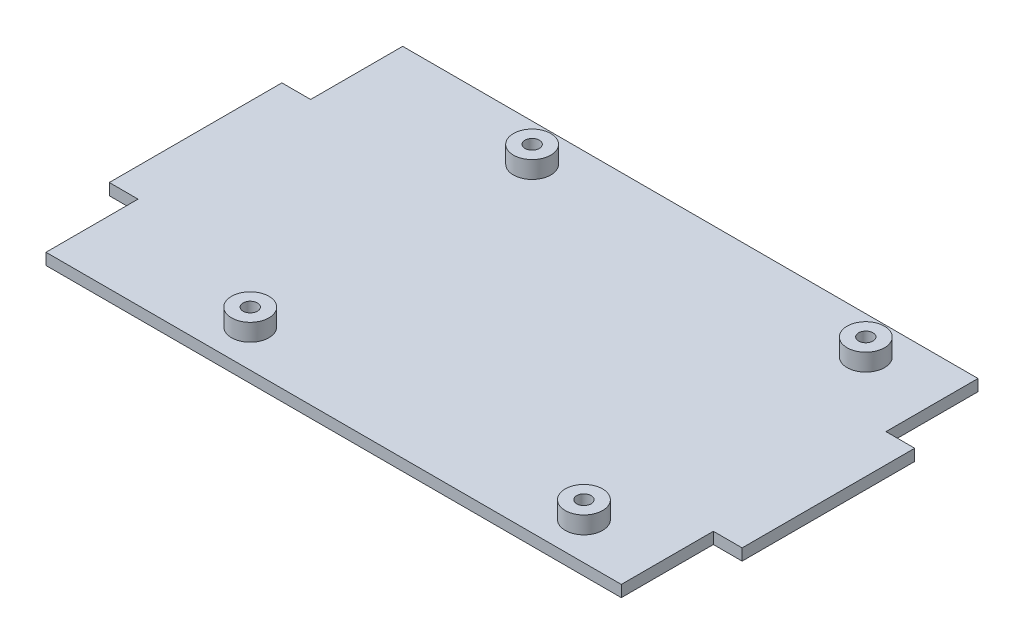
SolidWorks part; units mm, degrees
ref_plane "前视基准面" through (0, 0, 0) normal (0, 0, 1) x (1, 0, 0)
ref_plane "上视基准面" through (0, 0, 0) normal (0, 1, 0) x (1, 0, 0)
ref_plane "右视基准面" through (0, 0, 0) normal (1, 0, 0) x (0, 0, -1)
sketch "草图1" plane through (0, 0, 0) normal (0, 1, 0) x (1, 0, 0)
  line L1 (-50, 31) -> (50, 31)
  line L2 (-50, 31) -> (-50, -31)
  line L3 (-50, -31) -> (50, -31)
  line L4 (50, 31) -> (50, -31)
  line L5 (-50, 31) -> (50, -31) construction
  line L6 (-50, -31) -> (50, 31) construction
  line L7 (-55, 15) -> (55, 15)
  line L8 (-55, 15) -> (-55, -15)
  line L9 (-55, -15) -> (55, -15)
  line L10 (55, 15) -> (55, -15)
  line L11 (-55, 15) -> (55, -15) construction
  line L12 (-55, -15) -> (55, 15) construction
  point P0 (0, 0)
  point P6 (0, 0)
  dimension "D1" = 62
  dimension "D2" = 100
  dimension "D3" = 110
  dimension "D4" = 30
extrude "底板" add sketch "草图1" along normal blind 2 contours L8 L9 L10 L7 | L1 L4 L3 L2
sketch "草图2" plane through (0, 2, 0) normal (0, 1, 0) x (1, 0, 0)
  line L1 (-21, 24.5) -> (37, 24.5)
  line L2 (-21, 24.5) -> (-21, -24.5)
  line L3 (-21, -24.5) -> (37, -24.5)
  line L4 (37, 24.5) -> (37, -24.5)
  circle A0 centre (-21, 24.5) radius 1.25
  circle A1 centre (37, 24.5) radius 1.25
  circle A2 centre (-21, -24.5) radius 1.25
  circle A3 centre (37, -24.5) radius 1.25
  point P0 (0, 0)
  dimension "D3" = 2.5
  dimension "D4" = 2.5
  dimension "D5" = 2.5
  dimension "D6" = 2.5
  dimension "D1" = 49
  dimension "D2" = 58
  dimension "D7" = 37
extrude "螺丝孔" cut sketch "草图2" against normal blind 2 contours A0 | A2 | A3 | A1
sketch "草图3" plane through (0, 2, 0) normal (0, 1, 0) x (1, 0, 0)
  circle A0 centre (-21, 24.5) radius 1.25 construction
  circle A1 centre (-21, 24.5) radius 1.25
  circle A2 centre (37, 24.5) radius 1.25 construction
  circle A3 centre (37, 24.5) radius 1.25
  circle A4 centre (-21, -24.5) radius 1.25 construction
  circle A5 centre (-21, -24.5) radius 1.25
  circle A6 centre (37, -24.5) radius 1.25 construction
  circle A7 centre (37, -24.5) radius 1.25
  circle A8 centre (-21, 24.5) radius 3.25
  circle A9 centre (37, 24.5) radius 3.25
  circle A10 centre (-21, -24.5) radius 3.25
  circle A11 centre (37, -24.5) radius 3.25
  dimension "D1" = 2
extrude "螺丝架起" add sketch "草图3" along normal blind 3
